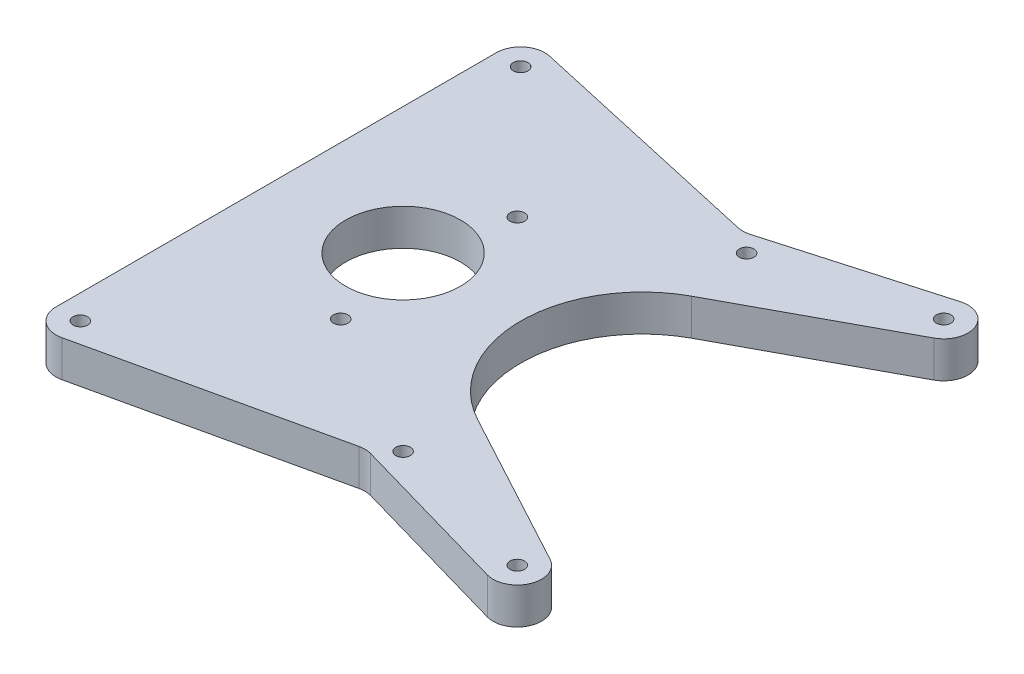
SolidWorks part; units mm, degrees
material "Alloy Steel"
ref_plane "Front Plane" through (0, 0, 0) normal (0, 0, 1) x (1, 0, 0)
ref_plane "Top Plane" through (0, 0, 0) normal (0, 1, 0) x (1, 0, 0)
ref_plane "Right Plane" through (0, 0, 0) normal (1, 0, 0) x (0, 0, -1)
sketch "Sketch2" plane through (0, 0, 0) normal (0, 1, 0) x (1, 0, 0)
  line L2 (62.5, 0) -> (25, 0) construction
  line L3 (25, 0) -> (0, 0) construction
  line L4 (62.5, 0) -> (179.6744, 0) construction
  line L5 (0, 0) -> (44.9013, 44.9013) construction
  line L6 (39.4146, 55.733) -> (62.5, 0) construction
  line L9 (62.5, 0) -> (85.5854, 55.733) construction
  line L10 (62.5, 0) -> (6.767, 23.0854) construction
  line L11 (0, 0) -> (-19.393, 0) construction
  line L12 (83.8387, 61.8381) -> (41.1613, 49.628)
  line L13 (38.0274, 49.5364) -> (-25.449, 63.7472)
  line L14 (0, 0) -> (-26.8363, 57.5505) construction
  line L15 (-25.449, -63.7472) -> (38.0274, -49.5364)
  line L16 (41.1613, -49.628) -> (83.8387, -61.8381)
  line L17 (0, 0) -> (44.9013, -44.9013) construction
  line L18 (-33.1863, 57.5505) -> (-33.1863, -57.5505)
  line L19 (0, 0) -> (-26.8363, -57.5505) construction
  line L21 (47.4315, 27.9464) -> (88.5991, 50.1438)
  line L22 (47.4315, -27.9464) -> (88.5991, -50.1438)
  arc A0 (47.4315, 27.9464) -> (47.4315, -27.9464) centre (62.5, 0) ccw
  circle A8 centre (6.767, 23.0854) radius 1.905
  circle A9 centre (85.5854, 55.733) radius 1.905
  circle A12 centre (85.5854, -55.733) radius 1.905
  circle A13 centre (6.767, -23.0854) radius 1.905
  circle A16 centre (0, 0) radius 25 construction
  circle A21 centre (85.5854, 55.733) radius 6.35
  circle A22 centre (85.5854, -55.733) radius 6.35
  circle A28 centre (0, 0) radius 15.0125
  circle A29 centre (-26.8363, 57.5505) radius 1.905
  circle A30 centre (44.9013, 44.9013) radius 1.905
  circle A33 centre (-26.8363, -57.5505) radius 1.905
  circle A34 centre (-26.8363, 57.5505) radius 6.35
  circle A35 centre (-26.8363, -57.5505) radius 6.35
  circle A37 centre (44.9013, -44.9013) radius 1.905
  circle A38 centre (39.4146, 55.733) radius 6.35
  circle A39 centre (39.4146, -55.733) radius 6.35
  dimension "D2" = 31.75
  dimension "D11" = 63.5
  dimension "D17" = 50
  dimension "D4" = 45
  dimension "D3" = 30.025
  dimension "D10" = 12.7
  dimension "D9" = 3.81
  dimension "D5" = 37.5
  dimension "D6" = 25
  dimension "D7" = 67.5
  dimension "D8" = 22.5
  dimension "D12" = 60.325
  dimension "D14" = 65
extrude "Boss-Extrude1" add sketch "Sketch2" along normal mid plane 9.525 contours A22 L22 A0 L21 A21 A16 | A13 | A22 A12 | A21 A9 | A8 | A34 A29 | A35 A33 region at (78.071, 0, -52.6742) region at (89.3003, 0, -60.6598) region at (-22.0201, 0, -61.4077) region at (90.8837, 0, 52.5704) region at (-26.8363, 0, 51.3801)
ref_axis "Turbine Axis" through (0, 55, 0) along (0, -1, 0)
ref_axis "Pump Axis" through (62.5, 4.7625, 0) along (0, -1, 0)
sketch "Sketch3" [suppressed] plane through (0, 0, 0) normal (0, 1, 0) x (1, 0, 0)
  line L1 (-30.2745, -68.3614) -> (223.7255, -68.3614)
  line L2 (-30.2745, -68.3614) -> (-30.2745, 185.6386)
  line L3 (-30.2745, 185.6386) -> (223.7255, 185.6386)
  line L4 (223.7255, -68.3614) -> (223.7255, 185.6386)
  dimension "D1" = 254
